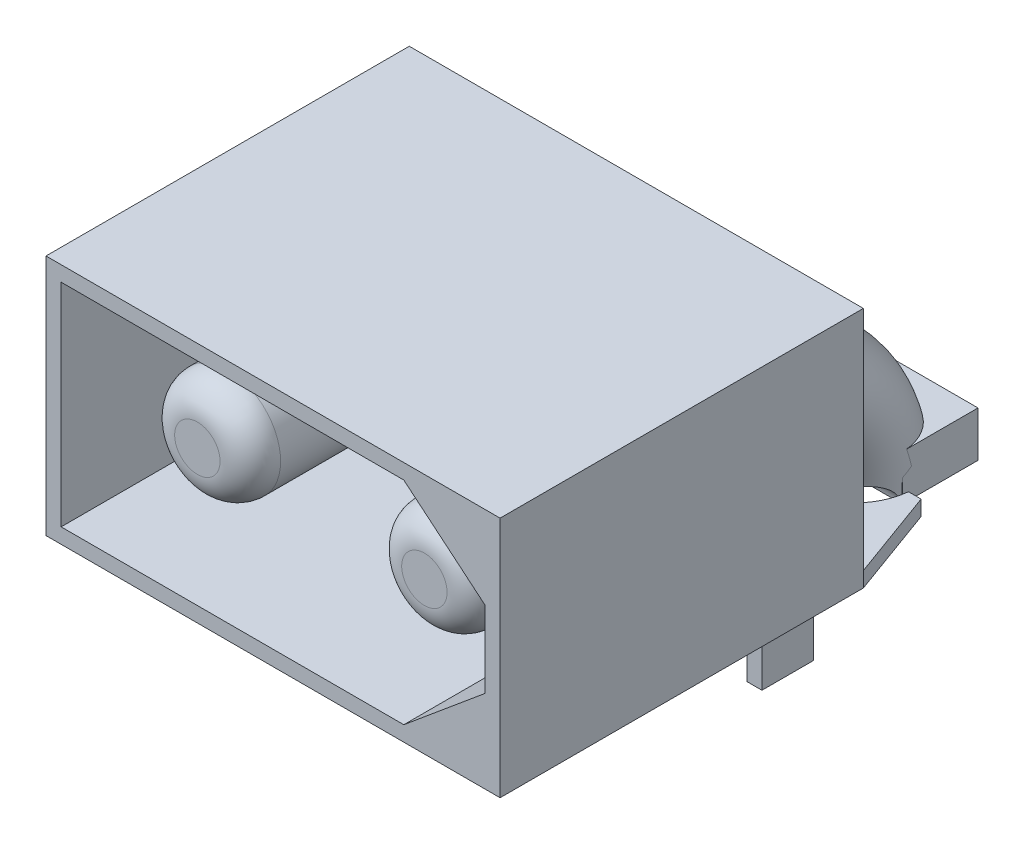
SolidWorks part; units mm, degrees
ref_plane "Front Plane" through (0, 0, 0) normal (0, 0, 1) x (1, 0, 0)
ref_plane "Top Plane" through (0, 0, 0) normal (0, 1, 0) x (1, 0, 0)
ref_plane "Right Plane" through (0, 0, 0) normal (1, 0, 0) x (0, 0, -1)
sketch "Sketch1" plane through (0, 0, 0) normal (0, 0, 1) x (1, 0, 0)
  line L0 (0, 0) -> (12, 0)
  line L1 (12, 0) -> (15, 2.5)
  line L2 (15, 2.5) -> (15, 5.5)
  line L3 (15, 5.5) -> (12, 8)
  line L4 (12, 8) -> (0, 8)
  line L5 (0, 8) -> (0, 0)
  line L6 (12, 8) -> (12, 0) construction
  line L7 (11.819, 7.5) -> (0.5, 7.5)
  line L8 (0.5, 7.5) -> (0.5, 0.5)
  line L9 (0.5, 0.5) -> (11.819, 0.5)
  line L10 (11.819, 0.5) -> (14.5, 2.7342)
  line L11 (14.5, 2.7342) -> (14.5, 5.2658)
  line L12 (14.5, 5.2658) -> (11.819, 7.5)
  line L13 (12, 8) -> (15, 8)
  line L14 (15, 8) -> (15, 0)
  line L15 (15, 0) -> (12, 0)
  dimension "D1" = 8
  dimension "D2" = 12
  dimension "D3" = 3
  dimension "D4" = 3
  dimension "D5" = 0.5
extrude "Boss-Extrude1" add sketch "Sketch1" along normal blind 10 contours L14 L13 L3 | L3 L6 L12 L11 L10 L1 L2 | L15 L14 L1 | L6 L4 L5 L0 L10 L9 L8 L7 L12 region at (0.1442, 4, 0) region at (12.0854, 0.3254, 0) region at (14, 0.8333, 0) region at (14, 7.1667, 0)
sketch "Sketch2" plane through (0, 0, 0) normal (0, 0, -1) x (-1, 0, 0)
  line L0 (-14.5, 2.7342) -> (-14.5, 5.2658) construction
  line L1 (-14.5, 2.7342) -> (-14.5, 5.2658)
  line L2 (-0.5, 7.5) -> (-14.5, 7.5)
  line L3 (-14.5, 7.5) -> (-14.5, 0.5)
  line L4 (-15, 8) -> (-15, 0)
  line L5 (-15, 0) -> (0, 0)
  line L6 (0, 0) -> (0, 8)
  line L7 (0, 8) -> (-15, 8)
  line L8 (-15, 8) -> (-15, 0)
  line L9 (-15, 0) -> (0, 0)
  line L10 (0, 0) -> (0, 8)
  line L11 (0, 8) -> (-15, 8)
  line L12 (-14.5, 0.5) -> (-0.5, 0.5)
  line L13 (-0.5, 0.5) -> (-0.5, 7.5)
  line L14 (-0.5, 7.5) -> (-11.819, 7.5)
  line L15 (-0.5, 0.5) -> (-0.5, 7.5)
  line L16 (-11.819, 0.5) -> (-0.5, 0.5)
  line L17 (-14.5, 2.7342) -> (-11.819, 0.5)
  line L18 (-14.5, 5.2658) -> (-14.5, 2.7342)
  line L19 (-11.819, 7.5) -> (-14.5, 5.2658)
  line L20 (-0.5, 7.5) -> (-11.819, 7.5)
  line L21 (-0.5, 0.5) -> (-0.5, 7.5)
  line L22 (-11.819, 0.5) -> (-0.5, 0.5)
  line L23 (-14.5, 2.7342) -> (-11.819, 0.5)
  line L24 (-14.5, 5.2658) -> (-14.5, 2.7342)
  line L25 (-11.819, 7.5) -> (-14.5, 5.2658)
  line M11 (-11.819, 7.5) -> (-0.5, 7.5)
  line M12 (-0.5, 7.5) -> (-0.5, 0.5)
  line M13 (-0.5, 0.5) -> (-11.819, 0.5)
  line M15 (-14.5, 2.7342) -> (-14.5, 5.2658)
  line M17 (-15, 8) -> (-15, 0)
  line M18 (-15, 0) -> (0, 0)
  line M19 (0, 0) -> (0, 8)
  line M20 (0, 8) -> (-15, 8)
  dimension "D1" = 0
  dimension "D2" = 0
  dimension "D3" = 0.5
extrude "Boss-Extrude2" add sketch "Sketch2" along normal blind 2 contours L12 L3 L2 M20 M17 M18 M19 M15 M11 M12 M13 region at (7.5, 7.83, 0)
sketch "Sketch3" plane through (0, 0, 0) normal (0, 0, 1) x (1, 0, 0)
  line L1 (0, 0) -> (15, 0)
  line L2 (0, 0) -> (0, 8)
  line L3 (0, 8) -> (15, 8)
  line L4 (15, 0) -> (15, 8)
extrude "Boss-Extrude3" add sketch "Sketch3" along normal blind 0.5
sketch "Sketch4" plane through (0, 0, 0.5) normal (0, 0, 1) x (1, 0, 0)
  line L0 (0.5, 4) -> (14.5, 4) construction
  line L1 (0.5, 0.5) -> (0.5, 7.5) construction
  line L2 (14.5, 2.7342) -> (14.5, 5.2658) construction
  line L3 (0, 8) -> (0, 0) construction
  circle A0 centre (4, 4) radius 1.75
  circle A1 centre (11.5, 4) radius 1.75
  point P10 (0, 4)
  dimension "D3" = 3.5
  dimension "D4" = 3.5
  dimension "D1" = 7.5
  dimension "D2" = 4
extrude "Boss-Extrude4" add sketch "Sketch4" along normal blind 8.5
fillet "Fillet1" radius 1 2 edges at (13.25, 4, 9) (5.75, 4, 9)
extrude "Boss-Extrude5" add sketch "Sketch4<2>" against normal blind 3
sketch "Sketch4<2>" plane through (0, 0, 0.5) normal (0, 0, 1) x (1, 0, 0) same geometry as "Sketch4"
sketch "Sketch5" plane through (0, 0, -2) normal (0, 0, -1) x (-1, 0, 0)
  line L0 (-15, 8) -> (-15, 0) construction
  line L1 (0, 0) -> (-15, 0)
  line L2 (0, 0) -> (0, 0.5)
  line L3 (0, 0.5) -> (-15, 0.5)
  line L4 (-15, 0) -> (-15, 0.5)
  line L5 (-14.5, 0.5) -> (-0.5, 0.5) construction
extrude "Boss-Extrude6" add sketch "Sketch5" along normal blind 3
chamfer "Chamfer1" distance 3 angle 20 2 edges at (0, 0.25, -5) (15, 0.25, -5) first distance on face at (0, 2.2083, 0.75) first distance on face at (15, 3.4583, 0.75)
sketch "Sketch6" plane through (0, 0, -2.5) normal (0, 0, -1) x (-1, 0, 0)
  circle A0 centre (-4, 4) radius 1.75
  circle A1 centre (-4, 4) radius 1.75 construction
  circle A3 centre (-11.5, 4) radius 1.75
  circle A4 centre (-11.5, 4) radius 1.75
  dimension "D1" = 0
ref_plane "Plane1" through (4, 0, 0) normal (-1, 0, 0) x (0, 0, 1)
sketch "Sketch7" plane through (4, 0, 0) normal (-1, 0, 0) x (0, 0, 1)
  line L0 (-5, 0) -> (-2, 0) construction
  line L1 (-2.5, 5.75) -> (-2.5, 2.25) construction
  line L4 (-2.5, 4) -> (10, 4) construction
  line L5 (10, 8) -> (10, 0) construction
  line L6 (-1.0138, 0) -> (-5.1968, 0.8434) construction
  arc A0 (-2.5, 4) -> (-5.1968, 0.8434) centre (-1.0138, 0) ccw
sweep "Sweep1" add profiles "Sketch6" path "Sketch7"
sketch "Sketch9" plane through (0, 0, 0) normal (0, -1, 0) x (1, 0, 0)
  circle A0 centre (11.5, -5.1968) radius 2
  circle A1 centre (4, -5.1968) radius 2
  dimension "D1" = 4
  dimension "D2" = 4
extrude "Cut-Extrude2" cut sketch "Sketch9" against normal mid plane 1.5
sketch "Sketch10" plane through (0, 0.75, 0) normal (0, -1, 0) x (1, 0, 0)
  line L0 (5.741, -5.046) -> (2.259, -5.046) construction
  line L1 (9.759, -5.046) -> (13.241, -5.046)
  line L2 (9.759, -5.046) -> (9.759, -7.546)
  line L3 (9.759, -7.546) -> (13.241, -7.546)
  line L4 (13.241, -5.046) -> (13.241, -7.546)
  line L5 (2.259, -5.046) -> (5.741, -5.046)
  line L6 (2.259, -5.046) -> (2.259, -7.546)
  line L7 (2.259, -7.546) -> (5.741, -7.546)
  line L8 (5.741, -5.046) -> (5.741, -7.546)
  ellipse E0 centre (4, -5.1968) end of major axis (2.25, -5.1968) minor radius 1.4876 (2.259, -5.046) -> (5.741, -5.046) ccw construction
  ellipse E1 centre (11.5, -5.1968) end of major axis (9.75, -5.1968) minor radius 1.4876 (9.759, -5.046) -> (13.241, -5.046) ccw construction
  dimension "D2" = 2.5
extrude "Boss-Extrude7" add sketch "Sketch10" along normal mid plane 1.5
fillet "Fillet9" radius 1 2 edges at (4, 0.75, -5.046) (11.5, 0.75, -5.046)
sketch "Sketch11" plane through (0, 0, 0) normal (0, -1, 0) x (1, 0, 0)
  line L0 (0, 10) -> (0, -2) construction
  line L1 (0, -1.1) -> (1.25, -1.1)
  line L2 (0, -1.1) -> (0, 0.6)
  line L3 (0, 0.6) -> (1.25, 0.6)
  line L4 (1.25, -1.1) -> (1.25, 0.6)
  line L5 (15, 10) -> (15, -2) construction
  line L6 (15, 0.6) -> (13.75, 0.6)
  line L7 (15, 0.6) -> (15, -1.1)
  line L8 (15, -1.1) -> (13.75, -1.1)
  line L9 (13.75, 0.6) -> (13.75, -1.1)
  line L10 (15, 10) -> (0, 10) construction
  line L11 (0.75, -1.1) -> (0.75, 0.6)
  line L12 (14.25, -1.1) -> (14.25, 0.6)
  dimension "D1" = 1.7
  dimension "D2" = 9.4
  dimension "D3" = 0.5
  dimension "D4" = 0.5
  dimension "D5" = 0.75
extrude "Boss-Extrude8" add sketch "Sketch11" along normal blind 2 contours L8 L12 L6 L9 | L11 L1 L4 L3 region at (1, 0, -0.25) region at (14, 0, -0.25)
